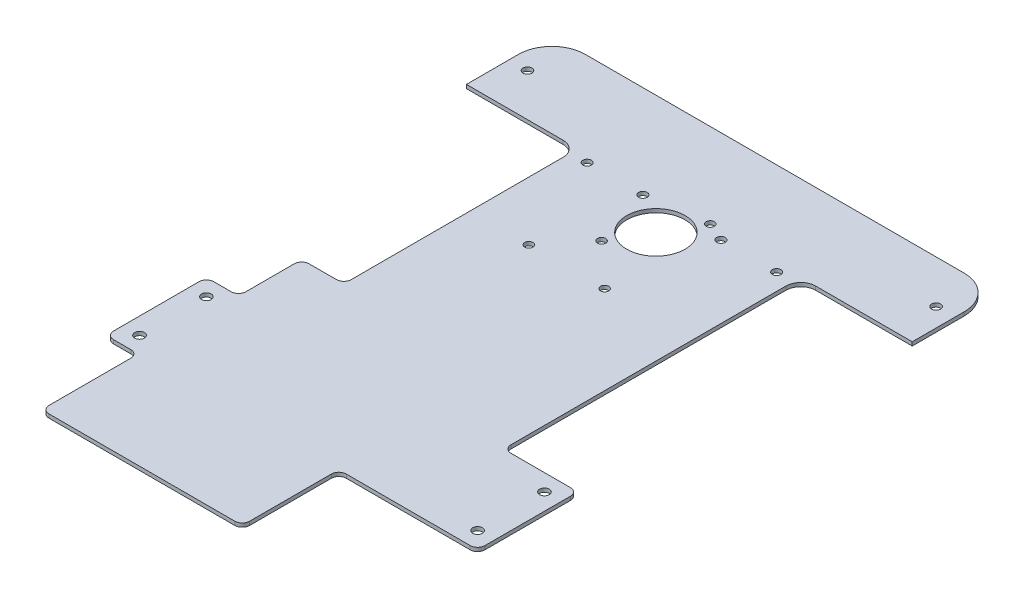
SolidWorks part; units mm, degrees
material "Thornel VCB-20 Carbon Cloth"
ref_plane "Front" through (0, 0, 0) normal (0, 0, 1) x (1, 0, 0)
ref_plane "Top" through (0, 0, 0) normal (0, 1, 0) x (1, 0, 0)
ref_plane "Right" through (0, 0, 0) normal (1, 0, 0) x (0, 0, -1)
ref_axis "X" through (-80.9, 0, 0) along (1, 0, 0)
ref_axis "Y" through (0, -50, 0) along (0, 1, 0)
ref_axis "Z" through (0, 0, -80.9) along (0, 0, 1)
sketch "Sketch1" plane through (0, 0, 0) normal (0, 1, 0) x (1, 0, 0)
  line L0 (-50, -130) -> (-41.35, -130)
  line L1 (-50, -130) -> (-50, -103)
  line L2 (-50, -103) -> (-41.35, -103)
  line L3 (-30, -86) -> (-30, -23)
  line L4 (-30, -23) -> (-60, -23)
  line L5 (-60, -23) -> (-60, 0)
  line L6 (-60, 0) -> (60, 0)
  line L7 (60, 0) -> (60, -23)
  line L8 (60, -23) -> (30, -23)
  line L9 (30, -23) -> (30, -103)
  line L10 (30, -103) -> (50, -103)
  line L11 (50, -103) -> (50, -130)
  line L12 (0, -162) -> (0, 0) construction
  line L13 (-41.35, -130) -> (-41.35, -156)
  line L14 (-41.35, -156) -> (12.65, -156)
  line L15 (12.65, -156) -> (12.65, -130)
  line L16 (12.65, -130) -> (50, -130)
  line L17 (-14.35, -156) -> (-14.35, -145.4675) construction
  line L18 (-41.35, -103) -> (-41.35, -86)
  line L19 (-41.35, -86) -> (-30, -86)
  dimension "D1" = 100
  dimension "D2" = 60
  dimension "D3" = 27
  dimension "D4" = 90
  dimension "D5" = 23
  dimension "D6" = 120
  dimension "D7" = 130
  dimension "D8" = 54
  dimension "D9" = 26
  dimension "D10" = 14.35
  dimension "D11" = 17
extrude "Boss-Extrude1" add sketch "Sketch1" along normal mid plane 1
hole_wizard "M2 Clearance Hole1" positions "Sketch2" profile "Sketch3" hole size "M2" standard "ANSI Metric" end condition up to next
sketch "Sketch2" plane through (0, 0.5, 0) normal (0, 1, 0) x (1, 0, 0)
  line L0 (-45.5, -125.5) -> (45.5, -125.5) construction
  line L2 (-50, -130) -> (-41.35, -130) construction
  line L3 (-50, -103) -> (-50, -130) construction
  line L4 (50, -130) -> (50, -103) construction
  line L5 (-45.5, -107.5) -> (-45.5, -125.5) construction
  line L8 (45.5, -107.5) -> (45.5, -125.5) construction
  point P0 (-45.5, -125.5)
  point P2 (45.5, -125.5)
  point P15 (-45.5, -107.5)
  point P17 (45.5, -107.5)
  dimension "D1" = 4.5
  dimension "D2" = 4.5
  dimension "D3" = 4.5
  dimension "D4" = 18
sketch "Sketch3" plane through (-45.5, 0.5, 125.5) normal (1, 0, 0) x (0, 0, 1)
  line L0 (0, 0) -> (0, 1)
  line L1 (0, 1) -> (1.3, 1)
  line L2 (1.3, 1) -> (1.3, 0)
  line L5 (1.3, 0) -> (0, 0)
  line L11 (0, -6.35) -> (0, 107.95) construction
  dimension "Thru Hole Dia." = 2.6
  dimension "Thru Hole Depth" = 1
fillet "Fillet1" radius 2 7 edges at (-50, 0, 130) (50, 0, 103) (-50, 0, 103) (-41.35, 0, 156) (12.65, 0, 156) (50, 0, 130) (-41.35, 0, 86)
fillet "Fillet2" radius 9 2 edges at (60, 0, 0) (-60, 0, 0)
hole_wizard "M2 Clearance Hole2" positions "Sketch7" profile "Sketch8" hole size "M2" standard "ANSI Metric" end condition up to next
sketch "Sketch7" plane through (0, 0.5, 0) normal (0, 1, 0) x (1, 0, 0)
  line L0 (-55, -11.57) -> (55, -11.57) construction
  line L2 (0, 0) -> (0, -11.57) construction
  line L3 (51, 0) -> (-51, 0) construction
  line L5 (-60, -23) -> (-30, -23) construction
  point P0 (-55, -11.57)
  point P2 (55, -11.57)
  dimension "D1" = 110
  dimension "D2" = 11.43
sketch "Sketch8" plane through (-55, 0.5, 11.57) normal (1, 0, 0) x (0, 0, 1)
  line L0 (0, 0) -> (0, 1)
  line L1 (0, 1) -> (1.2, 1)
  line L2 (1.2, 1) -> (1.2, 0)
  line L5 (1.2, 0) -> (0, 0)
  line L11 (0, -6.35) -> (0, 107.95) construction
  dimension "Thru Hole Dia." = 2.4
  dimension "Thru Hole Depth" = 1
fillet "Fillet4" radius 2 5 edges at (30, 0, 103) (12.65, 0, 130) (-41.35, 0, 130) (-30, 0, 86) (-41.35, 0, 103)
fillet "Fillet5" radius 4 2 edges at (30, 0, 23) (-30, 0, 23)
sketch "Sketch13" plane through (0, 0.5, 0) normal (0, 1, 0) x (1, 0, 0)
  line L0 (-38, -111) -> (-38, -122) construction
  line L1 (-35, -111) -> (-35, -122)
  line L3 (38, -111) -> (38, -122) construction
  line L5 (35, -111) -> (35, -122)
  line L6 (-38, -116.5) -> (38, -116.5) construction
  line L7 (0, -116.5) -> (0, 0) construction
  line L8 (51, 0) -> (-51, 0) construction
  line L11 (-45.5, -107.5) -> (-45.5, -125.5) construction
  line L12 (-45.5, -116.5) -> (-38, -116.5) construction
  line L13 (-38, -108) -> (-45.5, -108)
  line L14 (-38, -125) -> (-45.5, -125)
  line L15 (38, -108) -> (45.5, -108)
  line L16 (38, -125) -> (45.5, -125)
  line L17 (48.5, -111) -> (48.5, -122)
  line L18 (-48.5, -111) -> (-48.5, -122)
  line L19 (-35, -116.5) -> (-48.5, -116.5) construction
  line L20 (35, -116.5) -> (48.5, -116.5) construction
  arc A0 (-35, -111) -> (-38, -108) centre (-38, -111) ccw
  arc A1 (-38, -125) -> (-35, -122) centre (-38, -122) ccw
  arc A2 (38, -108) -> (35, -111) centre (38, -111) ccw
  arc A3 (35, -122) -> (38, -125) centre (38, -122) ccw
  circle A4 centre (-45.5, -107.5) radius 1.3 construction
  arc A5 (45.5, -108) -> (48.5, -111) centre (45.5, -111) cw
  arc A6 (48.5, -122) -> (45.5, -125) centre (45.5, -122) cw
  arc A7 (-45.5, -108) -> (-48.5, -111) centre (-45.5, -111) ccw
  arc A8 (-48.5, -122) -> (-45.5, -125) centre (-45.5, -122) ccw
  point P2 (-38, -116.5)
  point P8 (38, -116.5)
  dimension "D5" = 3.5
  dimension "D1" = 17
  dimension "D2" = 13.5
  dimension "D3" = 70
extrude "Cut-Extrude4" [suppressed] cut sketch "Sketch13" against normal through all
hole_wizard "M2 Clearance Hole3" positions "Sketch14" profile "Sketch15" hole size "M2" standard "ANSI Metric" end condition up to next
sketch "Sketch14" plane through (0, 0.5, 0) normal (0, 1, 0) x (1, 0, 0)
  line L2 (5.35, -22.7335) -> (-5.35, -41.2665) construction
  line L3 (0, 0) -> (0, -32) construction
  line L4 (51, 0) -> (-51, 0) construction
  point P0 (5.35, -22.7335)
  point P2 (-5.35, -41.2665)
  dimension "D1" = 21.4
  dimension "D2" = 32
  dimension "D3" = 30
sketch "Sketch15" plane through (5.35, 0.5, 22.7335) normal (1, 0, 0) x (0, 0, 1)
  line L0 (0, 0) -> (0, 1)
  line L1 (0, 1) -> (1.1, 1)
  line L2 (1.1, 1) -> (1.1, 0)
  line L5 (1.1, 0) -> (0, 0)
  line L11 (0, -6.35) -> (0, 107.95) construction
  dimension "Thru Hole Dia." = 2.2
  dimension "Thru Hole Depth" = 1
sketch "Sketch17" plane through (0, 0.5, 0) normal (0, 1, 0) x (1, 0, 0)
  line L0 (-25.5, -25) -> (-10.5, -25) construction
  line L1 (-10.5, -25) -> (10.5, -25) construction
  line L2 (10.5, -25) -> (25.5, -25) construction
  line L4 (0, -25) -> (0, 0) construction
  line L5 (-18, -25) -> (-18, -29.652) construction
  line L7 (51, 0) -> (-51, 0) construction
  line L8 (18, -25) -> (18, -28.4507) construction
  circle A8 centre (25.5, -25) radius 1.15
  circle A9 centre (10.5, -25) radius 1.15
  circle A10 centre (-10.5, -25) radius 1.15
  circle A11 centre (-25.5, -25) radius 1.15
  dimension "D7" = 2.3
  dimension "D1" = 15
  dimension "D2" = 36
  dimension "D4" = 25
extrude "Cut-Extrude6" cut sketch "Sketch17" against normal through all
sketch "Sketch18" plane through (0, 0.5, 0) normal (0, 1, 0) x (1, 0, 0)
  line L0 (5.35, -22.7335) -> (-5.35, -41.2665) construction
  circle A0 centre (0, -32) radius 7.85
  circle A6 centre (5.35, -22.7335) radius 1.1 construction
  circle A8 centre (-5.35, -41.2665) radius 1.1 construction
  dimension "D3" = 15.7
extrude "Cut-Extrude7" cut sketch "Sketch18" against normal up to next
hole_wizard "M2 Clearance Hole4" positions "Sketch19" profile "Sketch20" hole size "M2" standard "ANSI Metric" end condition up to next
sketch "Sketch19" plane through (0, 0.5, 0) normal (0, 1, 0) x (1, 0, 0)
  line L0 (-14.21, -52) -> (6.21, -52) construction
  line L2 (0, 0) -> (0, -52) construction
  line L3 (51, 0) -> (-51, 0) construction
  point P0 (-14.21, -52)
  point P2 (6.21, -52)
  dimension "D1" = 20.42
  dimension "D2" = 6.21
  dimension "D3" = 52
sketch "Sketch20" plane through (-14.21, 0.5, 52) normal (1, 0, 0) x (0, 0, 1)
  line L0 (0, 0) -> (0, 1)
  line L1 (0, 1) -> (1.1, 1)
  line L2 (1.1, 1) -> (1.1, 0)
  line L5 (1.1, 0) -> (0, 0)
  line L11 (0, -6.35) -> (0, 107.95) construction
  dimension "Thru Hole Dia." = 2.2
  dimension "Thru Hole Depth" = 1
equation "\"dd\"=4"
